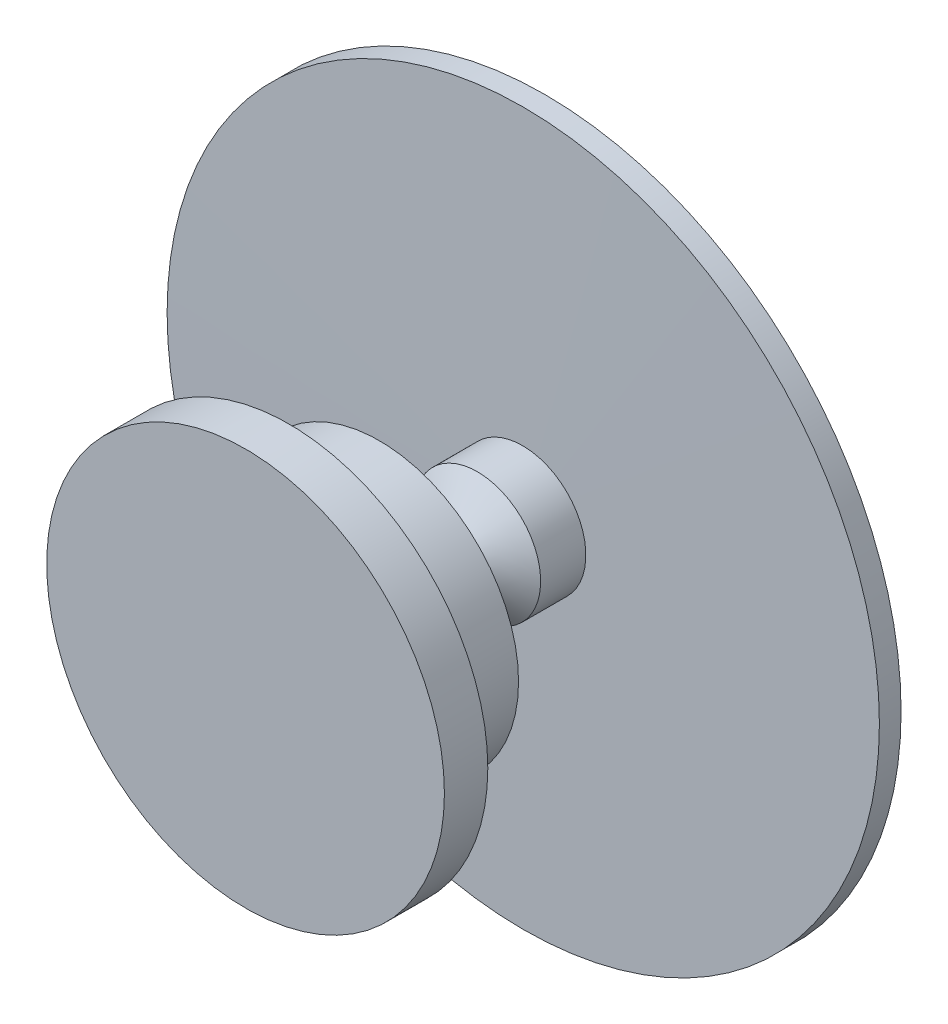
SolidWorks part; units mm, degrees
ref_plane "Front" through (0, 0, 0) normal (0, 0, 1) x (1, 0, 0)
ref_plane "Top" through (0, 0, 0) normal (0, 1, 0) x (1, 0, 0)
ref_plane "Right" through (0, 0, 0) normal (1, 0, 0) x (0, 0, -1)
sketch "Эскиз14" plane through (0, 0, 0) normal (0, 1, 0) x (1, 0, 0)
  line L0 (0, -600) -> (0, 0) construction
  line L1 (0, -441) -> (-110, -441)
  line L2 (-110, -441) -> (-110, -453)
  line L3 (-110, -453) -> (0, -453)
  line L4 (0, -441) -> (0, -453)
  dimension "D1" = 600
  dimension "D2" = 110
  dimension "D3" = 441
  dimension "D4" = 12
revolve "Повернуть11" add sketch "Эскиз14" angle 360 about L0
sketch "Эскиз15" plane through (0, 0, 0) normal (0, 1, 0) x (1, 0, 0)
  line L0 (0, 0) -> (0, -534.988) construction
  line L1 (-110, -441) -> (-110, -429)
  line L3 (-110, -441) -> (-75, -441)
  line L4 (110, -441) -> (-110, -441) construction
  line L5 (-75, -441) -> (-75, -381)
  line L6 (-75, -381) -> (-15, -381)
  line L7 (-15, -381) -> (-15, -379)
  line L8 (-110, -429) -> (-77, -429)
  line L9 (-15, -379) -> (-77, -379)
  line L10 (-77, -429) -> (-77, -379)
  dimension "D1" = 12
  dimension "D2" = 110
  dimension "D3" = 60
  dimension "D4" = 35
  dimension "D5" = 15
  dimension "D6" = 2
  dimension "D7" = 33
  dimension "D8" = 62
revolve "Повернуть12" add sketch "Эскиз15" angle 360 about L0
sketch "Эскиз16" plane through (0, 0, 0) normal (0, 1, 0) x (1, 0, 0)
  line L0 (0, 0) -> (0, -599.8085) construction
  line L1 (-15, -381) -> (-13, -381)
  line L4 (77, -379) -> (-77, -379) construction
  line L5 (-15, -381) -> (-15, -331)
  line L6 (-13, -381) -> (-13, -332.5)
  line L7 (-15, -331) -> (-13, -331)
  line L8 (-13, -332.5) -> (-11.5, -332.5)
  line L9 (-11.5, -332.5) -> (-11.5, -304.5)
  line L10 (-13, -331) -> (-13, -305.5)
  line L11 (-11.5, -304.5) -> (-18.2, -304.5)
  line L12 (-13, -305.5) -> (-15, -305.5)
  line L13 (-17.3, -307.5) -> (-15.7, -307.5)
  line L14 (-15.7, -307.5) -> (-15, -305.5)
  line L15 (-17.3, -307.5) -> (-18.2, -304.5)
  dimension "D1" = 2
  dimension "D2" = 13
  dimension "D3" = 2
  dimension "D4" = 50
  dimension "D5" = 1.5
  dimension "D6" = 1.5
  dimension "D7" = 28
  dimension "D8" = 27
  dimension "D9" = 6.7
  dimension "D10" = 2
  dimension "D11" = 2
  dimension "D12" = 4.3
  dimension "D13" = 1.6
revolve "Повернуть17" add sketch "Эскиз16" angle 360 about L0
sketch "Эскиз17" plane through (0, 0, 0) normal (0, 1, 0) x (1, 0, 0)
  line L0 (-15, -331) -> (-15, -379) construction
  line L1 (-15, -341) -> (-16.5, -341)
  line L2 (77, -379) -> (-77, -379) construction
  line L3 (-16.5, -341) -> (-16.5, -338)
  line L4 (-15, -341) -> (-15, -336.62)
  line L5 (-13, -323.4) -> (-33.5, -323.4)
  line L6 (15, -331) -> (-15, -331) construction
  line L7 (-13, -305.5) -> (-13, -331) construction
  line L8 (-15, -336.62) -> (-33.5, -323.4)
  line L9 (-16.5, -338) -> (-35, -324.78)
  line L10 (-33.5, -323.4) -> (-33.5, -283.4)
  line L11 (-35, -324.78) -> (-35, -299.78)
  line L12 (-33.5, -283.4) -> (-159.5, -283.4)
  line L13 (-159.5, -283.4) -> (-159.5, -287.4)
  line L14 (-159.5, -287.4) -> (-197, -287.4)
  line L15 (-197, -287.4) -> (-197, -299.4)
  line L16 (-197, -299.4) -> (-35, -299.78)
  line L17 (0, 0) -> (0, -530.5891) construction
  dimension "D7" = 40
  dimension "D1" = 38
  dimension "D2" = 1.5
  dimension "D3" = 3
  dimension "D4" = 4.38
  dimension "D5" = 7.6
  dimension "D6" = 20.5
  dimension "D8" = 25
  dimension "D9" = 126
  dimension "D10" = 4
  dimension "D11" = 37.5
  dimension "D12" = 12
revolve "Повернуть19" add sketch "Эскиз17" angle 360 about L17 region at (-108.3238, 0, 292.9284)
sketch "Эскиз18" plane through (0, 0, 0) normal (0, 1, 0) x (1, 0, 0)
  line L0 (-197, -287.4) -> (-197, -275.4)
  line L1 (-197, -287.4) -> (-170, -287.4)
  line L2 (197, -287.4) -> (-197, -287.4) construction
  line L3 (-170, -287.4) -> (-170, -282.4)
  line L4 (-170, -282.4) -> (-165, -282.4)
  line L5 (-165, -282.4) -> (-165, -287.4)
  line L6 (-165, -287.4) -> (-160, -287.4)
  line L7 (-160, -287.4) -> (-160, -6.4)
  line L8 (-197, -275.4) -> (-170, -275.4)
  line L9 (-170, -275.4) -> (-170, -277.4)
  line L10 (-170, -277.4) -> (-166, -277.4)
  line L11 (-166, -277.4) -> (-166, -275.4)
  line L12 (-166, -275.4) -> (-164, -275.4)
  line L13 (-164, -275.4) -> (-164, 1.6)
  dimension "D1" = 12
  dimension "D2" = 27
  dimension "D3" = 5
  dimension "D4" = 5
  dimension "D5" = 5
  dimension "D6" = 281
  dimension "D7" = 27
  dimension "D8" = 2
  dimension "D9" = 4
  dimension "D10" = 2
  dimension "D11" = 277
